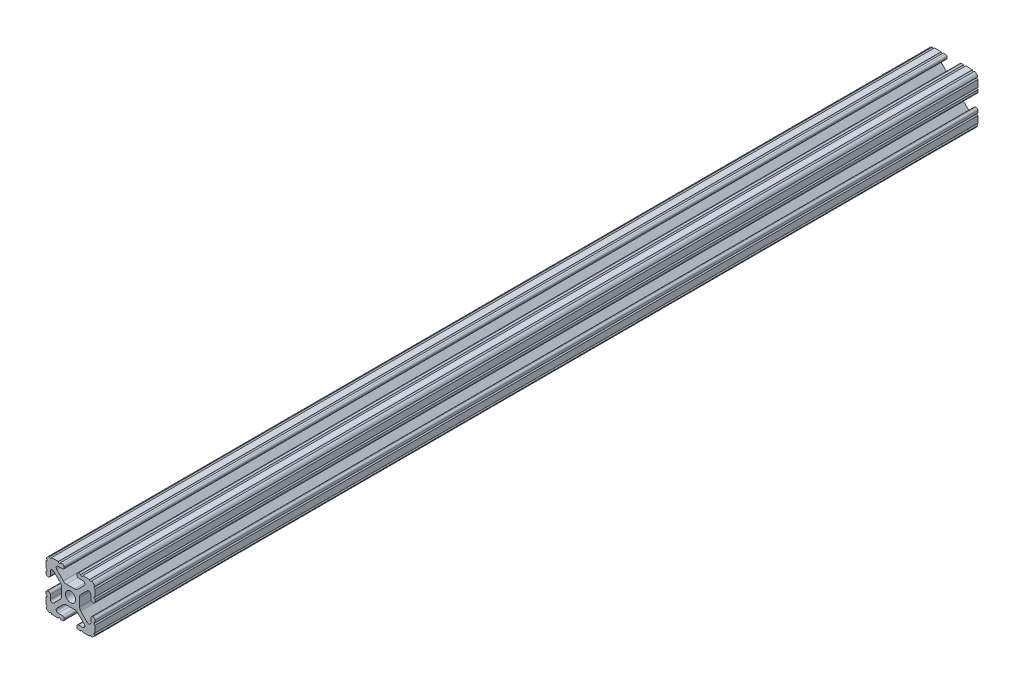
SolidWorks part; units mm, degrees
ref_plane "Front Plane" through (0, 0, 0) normal (0, 0, 1) x (1, 0, 0)
ref_plane "Top Plane" through (0, 0, 0) normal (0, 1, 0) x (1, 0, 0)
ref_plane "Right Plane" through (0, 0, 0) normal (1, 0, 0) x (0, 0, -1)
sketch "Sketch2" plane through (0, 0, 0) normal (0, 0, 1) x (1, 0, 0)
  line L0 (0, 12.7) -> (0, -12.7) construction
  line L1 (-12.7, 0) -> (12.7, 0) construction
  line L2 (3.2512, -12.7) -> (12.7, -12.7)
  line L3 (12.7, -12.7) -> (12.7, -3.2512)
  line L4 (3.2512, -12.7) -> (3.2512, -10.4902)
  line L5 (3.2512, -10.4902) -> (8.9276, -10.4902)
  line L6 (8.9276, -10.4902) -> (3.0856, -4.6482)
  line L7 (0, 0) -> (12.7, -12.7) construction
  line L8 (12.7, -3.2512) -> (10.4902, -3.2512)
  line L9 (10.4902, -3.2512) -> (10.4902, -8.9276)
  line L10 (10.4902, -8.9276) -> (4.6482, -3.0856)
  circle A0 centre (0, 0) radius 2.6035
  arc A1 (6.3485, -10.4902) -> (7.1039, -8.6665) centre (6.3485, -9.4219) ccw construction
  point P8 (0, -4.6482)
  dimension "Center Hole Diameter" = 5.207
  dimension "Rail Height" = 25.4
  dimension "Rail Width" = 25.4
  dimension "T-Slot Width" = 6.5024
  dimension "Slot Inner Width" = 14.8336
  dimension "Thickness" = 2.2098
  dimension "Slot Depth" = 5.842
  dimension "D1" = 2.2098
sketch "Sketch3" plane through (0, 0, 0) normal (1, 0, 0) x (0, 0, -1)
  line L0 (-228.6, -12.7) -> (228.6, -12.7) construction
  line L1 (-203.2, 0) -> (203.2, 0) construction
  dimension "Length" = 457.2
sketch "Sketch4" plane through (0, 0, 0) normal (0, 0, 1) x (1, 0, 0)
  line L0 (4.1904, -12.7) -> (10.1173, -12.7)
  line L1 (3.2512, -12.7) -> (12.7, -12.7) construction
  line L2 (3.2512, -12.7) -> (3.2512, -10.4902) construction
  line L3 (3.2512, -10.4902) -> (8.9276, -10.4902) construction
  line L4 (3.2512, -11.4294) -> (3.2512, -11.7608)
  line L5 (4.1904, -10.4902) -> (6.3485, -10.4902)
  line L6 (0, -4.6482) -> (2.164, -4.6482)
  line L7 (8.9276, -10.4902) -> (3.0856, -4.6482) construction
  line L8 (3.7373, -5.2999) -> (7.1039, -8.6665)
  line L9 (12.7, -12.7) -> (12.7, -3.2512) construction
  line L10 (10.4902, -8.9276) -> (4.6482, -3.0856) construction
  line L11 (10.4902, -3.2512) -> (10.4902, -8.9276) construction
  line L12 (10.4902, -6.3485) -> (10.4902, -4.1904)
  line L13 (12.7, -3.2512) -> (10.4902, -3.2512) construction
  line L14 (11.4294, -3.2512) -> (11.7608, -3.2512)
  line L15 (12.7, -4.1904) -> (12.7, -10.1173)
  line L16 (8.6665, -7.1039) -> (5.2999, -3.7373)
  line L17 (4.6482, 0) -> (4.6482, -2.164)
  line L18 (-12.7, 0) -> (12.7, 0) construction
  line L19 (0, -4.6482) -> (0, -2.6035)
  line L20 (0, 12.7) -> (0, -12.7) construction
  line L21 (4.6482, 0) -> (2.6035, 0)
  arc A0 (3.2512, -11.7608) -> (4.1904, -12.7) centre (4.1904, -11.7608) ccw
  arc A2 (3.2512, -11.4294) -> (4.1904, -10.4902) centre (4.1904, -11.4294) cw
  arc A3 (6.3485, -10.4902) -> (7.1039, -8.6665) centre (6.3485, -9.4219) ccw
  arc A4 (2.164, -4.6482) -> (3.7373, -5.2999) centre (2.164, -6.8732) cw
  arc A5 (10.1173, -12.7) -> (12.7, -10.1173) centre (10.1173, -10.1173) ccw
  arc A6 (8.6665, -7.1039) -> (10.4902, -6.3485) centre (9.4219, -6.3485) ccw
  arc A7 (10.4902, -4.1904) -> (11.4294, -3.2512) centre (11.4294, -4.1904) cw
  arc A8 (11.7608, -3.2512) -> (12.7, -4.1904) centre (11.7608, -4.1904) cw
  arc A9 (5.2999, -3.7373) -> (4.6482, -2.164) centre (6.8732, -2.164) cw
  circle A10 centre (0, 0) radius 2.6035 construction
  arc A11 (0, -2.6035) -> (2.6035, 0) centre (0, 0) ccw
  dimension "D1" = 2.5827
  dimension "D2" = 2.225
  dimension "D3" = 0.9392
extrude "Boss-Extrude1" add sketch "Sketch4" along normal mid plane 457.2
sketch "Sketch5" plane through (0, 0, 0) normal (0, 0, 1) x (1, 0, 0)
  line L0 (3.2512, -12.7) -> (12.7, -12.7) construction
  line L1 (4.1904, -10.4902) -> (6.3485, -10.4902) construction
  line L3 (0, 0) -> (12.7, -12.7) construction
  line L4 (6.3485, -10.4902) -> (6.3485, -12.7) construction
  line L5 (8.9276, -10.4902) -> (3.0856, -4.6482) construction
  circle A0 centre (10.3562, -12.7) radius 0.5524
  circle A1 centre (5.796, -12.7) radius 0.5524
  circle A2 centre (12.7, -10.3562) radius 0.5524
  circle A3 centre (12.7, -5.796) radius 0.5524
  point P10 (5.2694, -10.4902)
  point P12 (9.4219, -6.3485)
  dimension "D1" = 1.1049
extrude "Cut-Extrude1" cut sketch "Sketch5" against normal through all both and the other way through all
mirror "Mirror1" about plane through (0, 0, 0) normal (1, 0, 0) of bodies 137 134
mirror "Mirror2" about plane through (0, 0, 0) normal (0, 1, 0) of bodies 135
equation "\"D1@Boss-Extrude1\"=\"Length@Sketch3\""
equation "\"D1@Sketch2\"=\"Thickness@Sketch2\""
equation "\"D2@Sketch4\"=\"Slot Inner Width@Sketch2\"*0.15"
equation "\"D1@Sketch4\"=\"D3@Sketch4\"*2.75"
equation "\"D3@Sketch4\"=\"Thickness@Sketch2\"*0.425"
equation "\"D1@Sketch5\"=\"Thickness@Sketch2\"*0.5"
